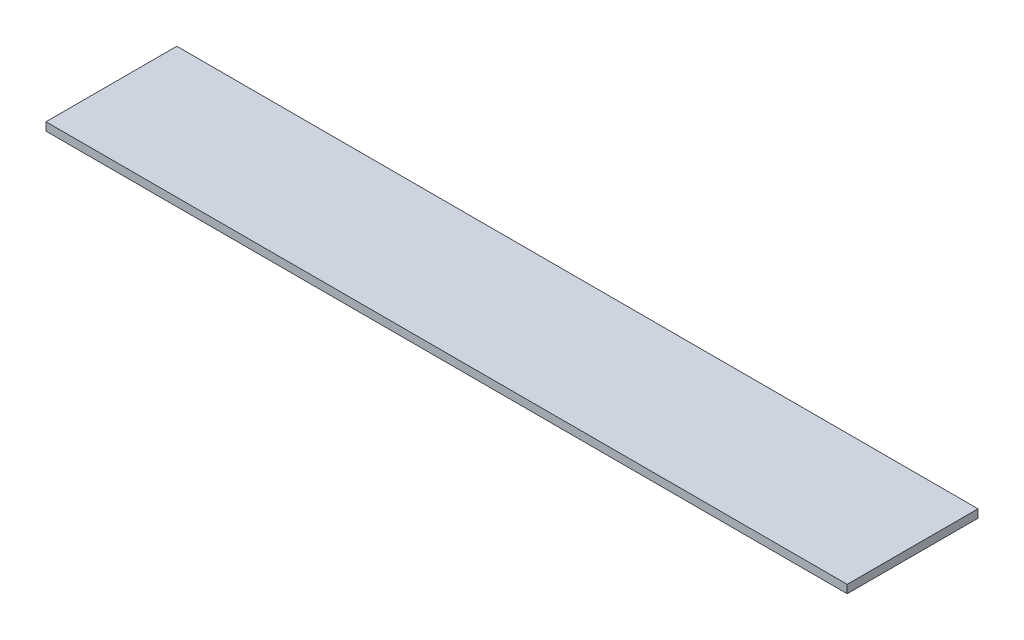
SolidWorks part; units mm, degrees
material "Acrylic (Medium-high impact)"
ref_plane "Front Plane" through (0, 0, 0) normal (0, 0, 1) x (1, 0, 0)
ref_plane "Top Plane" through (0, 0, 0) normal (0, 1, 0) x (1, 0, 0)
ref_plane "Right Plane" through (0, 0, 0) normal (1, 0, 0) x (0, 0, -1)
sketch "Sketch1" plane through (0, 0, 0) normal (0, 1, 0) x (1, 0, 0)
  line L1 (-311.15, -50.8) -> (311.15, -50.8)
  line L2 (-311.15, -50.8) -> (-311.15, 50.8)
  line L3 (-311.15, 50.8) -> (311.15, 50.8)
  line L4 (311.15, -50.8) -> (311.15, 50.8)
  line L5 (-311.15, -50.8) -> (311.15, 50.8) construction
  line L6 (-311.15, 50.8) -> (311.15, -50.8) construction
  line L7 (234.95, -50.8) -> (31.75, -50.8)
  line L11 (-222.25, -50.8) -> (-69.85, -50.8)
  point P0 (0, 0)
  dimension "D1" = 622.3
  dimension "D2" = 101.6
extrude "Boss-Extrude1" add sketch "Sketch1" along normal mid plane 6.35 contours L1 L4 L3 L2 region at (0, 0, 0)
sketch "Sketch2" plane through (0, 0, 0) normal (0, 1, 0) x (1, 0, 0)
  line L0 (-311.15, -50.8) -> (311.15, -50.8) construction
  line L1 (234.95, -50.8) -> (19.05, -50.8)
  line L2 (234.95, -50.8) -> (234.95, -95.25)
  line L3 (234.95, -95.25) -> (19.05, -95.25)
  line L4 (19.05, -50.8) -> (19.05, -95.25)
  line L6 (-82.55, -50.8) -> (-234.95, -50.8)
  line L7 (-82.55, -50.8) -> (-82.55, -95.25)
  line L8 (-82.55, -95.25) -> (-234.95, -95.25)
  line L9 (-234.95, -50.8) -> (-234.95, -95.25)
  line L10 (311.15, -50.8) -> (311.15, 50.8) construction
  line L11 (-311.15, -50.8) -> (-311.15, 50.8) construction
  line L12 (-311.15, 50.8) -> (311.15, 50.8) construction
  dimension "D1" = 101.6
  dimension "D2" = 76.2
  dimension "D3" = 76.2
  dimension "D4" = 228.6
  dimension "D5" = 146.05
extrude "Boss-Extrude2" [suppressed] add sketch "Sketch2" along normal mid plane 6.35 contours L6 L9 L8 L7 | L2 L3 L4 L1
